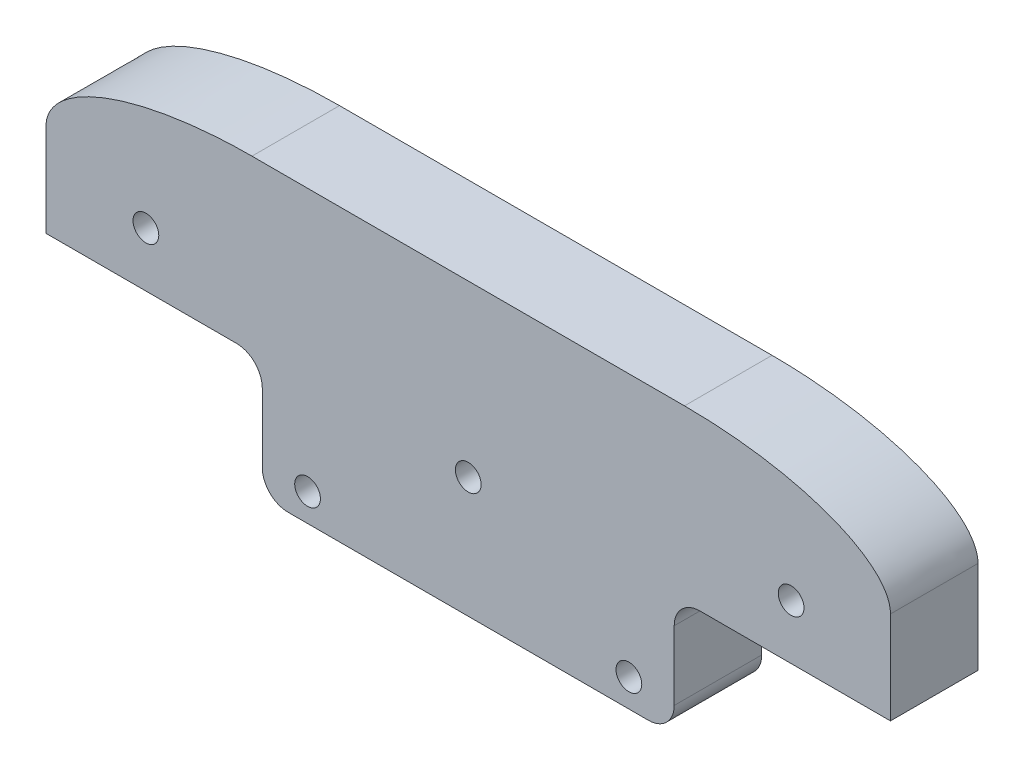
SolidWorks part; units mm, degrees
ref_plane "前视基准面" through (0, 0, 0) normal (0, 0, 1) x (1, 0, 0)
ref_plane "上视基准面" through (0, 0, 0) normal (0, 1, 0) x (1, 0, 0)
ref_plane "右视基准面" through (0, 0, 0) normal (1, 0, 0) x (0, 0, -1)
sketch "草图1" plane through (0, 0, 0) normal (0, 0, 1) x (1, 0, 0)
  line L0 (-110.6884, 34) -> (29.8938, 34) construction
  line L1 (0, 0) -> (-80, 0)
  line L2 (0, 0) -> (0, 23.4)
  line L3 (0, 23.4) -> (-80, 23.4)
  line L4 (-80, 0) -> (-80, 23.4)
  line L5 (-122, 56.39) -> (42, 56.39)
  line L6 (-122, 56.39) -> (-122, 23.4)
  line L7 (-122, 23.4) -> (42, 23.4)
  line L8 (42, 56.39) -> (42, 23.4)
  line L9 (-76.2643, 5.4) -> (-3.4996, 5.4) construction
  circle A0 centre (-71.2, 5.4) radius 2.5
  circle A1 centre (-8.8, 5.4) radius 2.5
  circle A2 centre (-40, 23.4) radius 2.5
  circle A3 centre (-102.6, 34) radius 2.5
  circle A4 centre (22.705, 34) radius 2.5
  dimension "D7" = 5
  dimension "D8" = 5
  dimension "D9" = 5
  dimension "D10" = 5
  dimension "D11" = 5
  dimension "D17" = 8.8
  dimension "D1" = 80
  dimension "D2" = 56.39
  dimension "D3" = 164
  dimension "D4" = 0
  dimension "D5" = 23.4
  dimension "D6" = 42
  dimension "D12" = 62.4
  dimension "D13" = 28.6
  dimension "D14" = 34
  dimension "D15" = 19.4
  dimension "D16" = 125.305
  dimension "D18" = 0
  dimension "D19" = 8.8
extrude "凸台-拉伸1" add sketch "草图1" along normal blind 17 contours A2 L3 L7 L8 L5 L6 A4 A3 | A2 L3 L4 L1 L2 A1 A0 region at (-40, 11.7784, 0) region at (-40.0004, 39.9664, 0)
fillet "圆角1" radius 40 2 edges at (42, 56.39, 8.5) (-122, 56.39, 8.5) second distance 15 first distance on face at (-40, 56.39, 8.5)
fillet "圆角2" radius 5 4 edges at (0, 0, 8.5) (-80, 0, 8.5) (0, 23.4, 8.5) (-80, 23.4, 8.5)
